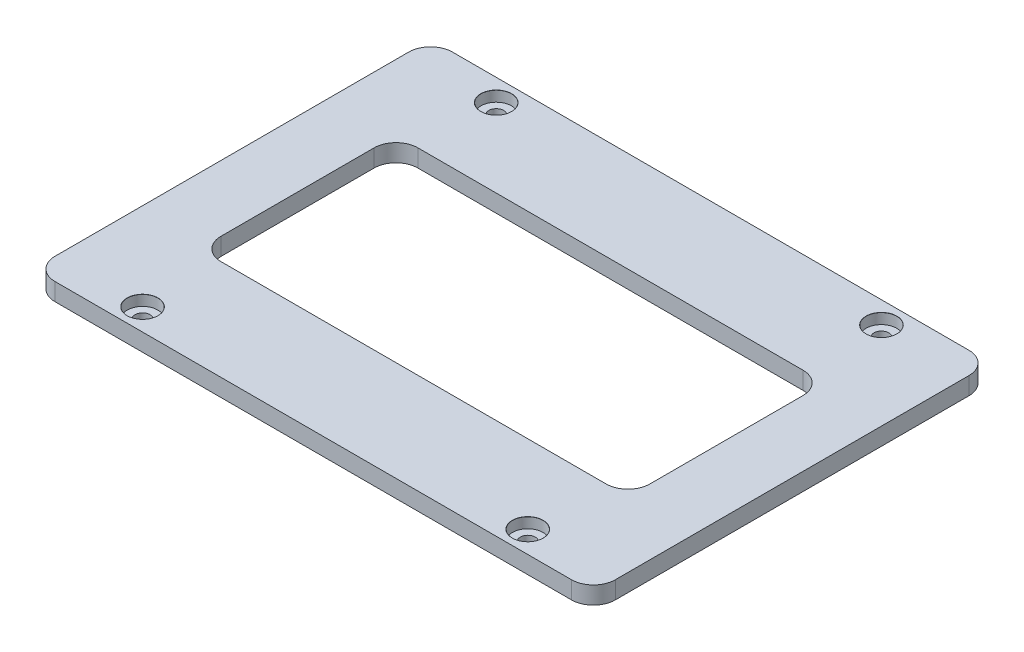
SolidWorks part; units mm, degrees
ref_plane "Front Plane" through (0, 0, 0) normal (0, 0, 1) x (1, 0, 0)
ref_plane "Top Plane" through (0, 0, 0) normal (0, 1, 0) x (1, 0, 0)
ref_plane "Right Plane" through (0, 0, 0) normal (1, 0, 0) x (0, 0, -1)
sketch "Sketch1" plane through (0, 0, 0) normal (0, 1, 0) x (1, 0, 0)
  line L1 (-64, 45.4) -> (64, 45.4)
  line L2 (-64, 45.4) -> (-64, -45.4)
  line L3 (-64, -45.4) -> (64, -45.4)
  line L4 (64, 45.4) -> (64, -45.4)
  line L5 (-64, 45.4) -> (64, -45.4) construction
  line L6 (-64, -45.4) -> (64, 45.4) construction
  point P0 (0, 0)
  dimension "D1" = 90.8
  dimension "D2" = 128
extrude "Boss-Extrude1" add sketch "Sketch1" along normal blind 4
sketch "Sketch2" plane through (0, 4, 0) normal (0, 1, 0) x (1, 0, 0)
  line L1 (-49, 22.5) -> (49, 22.5)
  line L2 (-49, 22.5) -> (-49, -22.5)
  line L3 (-49, -22.5) -> (49, -22.5)
  line L4 (49, 22.5) -> (49, -22.5)
  line L5 (-49, 22.5) -> (49, -22.5) construction
  line L6 (-49, -22.5) -> (49, 22.5) construction
  point P0 (0, 0)
  dimension "D1" = 45
  dimension "D2" = 98
extrude "Cut-Extrude1" cut sketch "Sketch2" against normal blind 4
sketch "Sketch3" plane through (0, 4, 0) normal (0, 1, 0) x (1, 0, 0)
  line L0 (-44, 40.4) -> (44, 40.4) construction
  line L1 (44, 40.4) -> (44, -40.4) construction
  line L2 (44, -40.4) -> (-44, -40.4) construction
  line L3 (-44, -40.4) -> (-44, 40.4) construction
  line L4 (-64, 45.4) -> (-64, -45.4) construction
  line L5 (64, 45.4) -> (-64, 45.4) construction
  line L6 (-64, -45.4) -> (64, -45.4) construction
  line L7 (64, -45.4) -> (64, 45.4) construction
  point P0 (-44, 40.4)
  point P1 (44, 40.4)
  point P2 (-44, -40.4)
  point P3 (44, -40.4)
  dimension "D1" = 20
  dimension "D2" = 5
  dimension "D3" = 5
  dimension "D4" = 20
hole_wizard "CBORE for M3 Pan Head Machine Screw1" positions "Sketch4" profile "Sketch5" counterbore size "M3" standard "ANSI Metric" end condition through all
sketch "Sketch4" plane through (0, 4, 0) normal (0, 1, 0) x (1, 0, 0)
  point P0 (-44, 40.4)
  point P3 (44, 40.4)
  point P6 (44, -40.4)
  point P9 (-44, -40.4)
sketch "Sketch5" plane through (-44, 4, -40.4) normal (1, 0, 0) x (0, 0, 1)
  line L0 (0, 0) -> (0, 4)
  line L1 (0, 4) -> (1.7, 4)
  line L3 (1.7, 4) -> (1.7, 2.4)
  line L4 (3.5, 2.4) -> (1.7, 2.4)
  line L5 (3.5, 2.4) -> (3.5, 0.025)
  line L6 (3.5, 0.025) -> (3.525, 0)
  line L7 (3.525, 0) -> (0, 0)
  line L8 (-3.5, 0.025) -> (-3.525, 0) construction
  line L11 (0, -6.35) -> (0, 107.95) construction
  dimension "Thru Hole Dia." = 3.4
  dimension "Thru Hole Depth" = 4
  dimension "C'Bore Dia." = 7
  dimension "C'Bore Depth" = 2.4
  dimension "Near C'Sink Dia." = 7.05
  dimension "Near C'Sink Angle" = 90
fillet "Fillet1" radius 5 8 edges at (49, 2, 22.5) (-49, 2, 22.5) (49, 2, -22.5) (-49, 2, -22.5) (64, 2, -45.4) (64, 2, 45.4) (-64, 2, 45.4) (-64, 2, -45.4)
